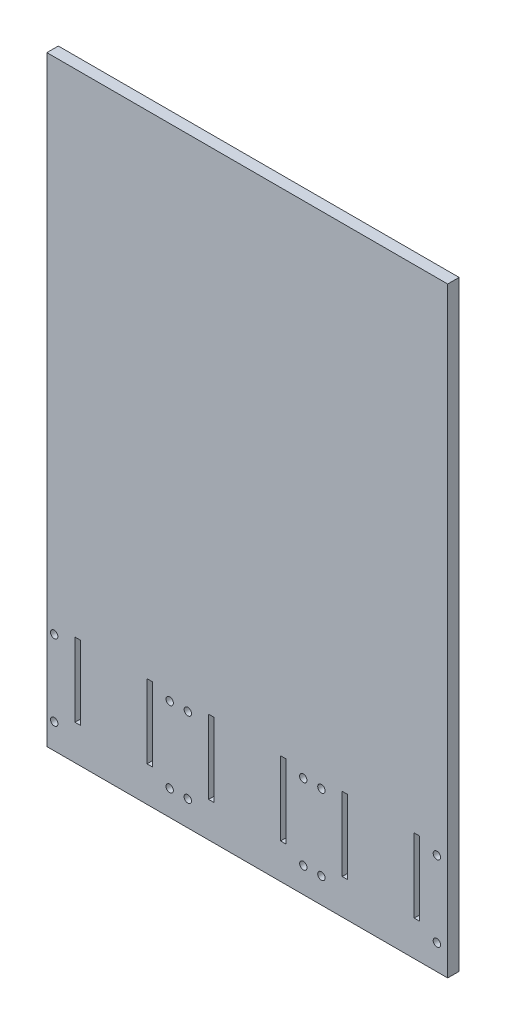
SolidWorks part; units mm, degrees
ref_plane "Front Plane" through (0, 0, 0) normal (0, 0, 1) x (1, 0, 0)
ref_plane "Top Plane" through (0, 0, 0) normal (0, 1, 0) x (1, 0, 0)
ref_plane "Right Plane" through (0, 0, 0) normal (1, 0, 0) x (0, 0, -1)
sketch "Sketch1" plane through (0, 0, 0) normal (0, 0, 1) x (1, 0, 0)
  line L0 (111.3, -111.5408) -> (111.3, 222.2553)
  line L1 (111.3, -111.5408) -> (-111.3, -111.5408)
  line L2 (111.3, 222.2553) -> (-111.3, 222.2553)
  line L3 (-111.3, -111.5408) -> (-111.3, 222.2553)
  line L4 (111.3, -111.5408) -> (-111.3, 222.2553) construction
  line L5 (111.3, 222.2553) -> (-111.3, -111.5408) construction
  line L6 (-95.7, -103.393) -> (-95.7, -89.9338) construction
  line L7 (-95.7, -51.0408) -> (-92.7, -51.0408)
  line L8 (-95.7, -51.0408) -> (-95.7, -92.0408)
  line L9 (-95.7, -92.0408) -> (-92.7, -92.0408)
  line L10 (-92.7, -51.0408) -> (-92.7, -92.0408)
  line L11 (-92.7, -104.2814) -> (-92.7, -92.5342) construction
  line L12 (-95.7, -51.5408) -> (-92.7, -51.5408) construction
  line L13 (-55.7, -107.2088) -> (-55.7, -104.2814) construction
  line L14 (-55.7, -51.0408) -> (-52.7, -51.0408)
  line L15 (-55.7, -51.0408) -> (-55.7, -92.0408)
  line L16 (-55.7, -92.0408) -> (-52.7, -92.0408)
  line L17 (-52.7, -51.0408) -> (-52.7, -92.0408)
  line L18 (-52.7, -103.393) -> (-52.7, -89.9338) construction
  line L20 (-52.7, -51.5408) -> (-55.7, -51.5408) construction
  line L22 (18.5, -51.0408) -> (18.5, -92.0408)
  line L23 (18.5, -51.0408) -> (21.5, -51.0408)
  line L24 (21.5, -51.0408) -> (21.5, -92.0408)
  line L25 (18.5, -92.0408) -> (21.5, -92.0408)
  line L26 (-21.5, -51.0408) -> (-21.5, -92.0408)
  line L27 (-21.5, -51.0408) -> (-18.5, -51.0408)
  line L28 (-18.5, -51.0408) -> (-18.5, -92.0408)
  line L29 (-21.5, -92.0408) -> (-18.5, -92.0408)
  line L30 (92.7, -51.0408) -> (92.7, -92.0408)
  line L31 (92.7, -51.0408) -> (95.7, -51.0408)
  line L32 (95.7, -51.0408) -> (95.7, -92.0408)
  line L33 (92.7, -92.0408) -> (95.7, -92.0408)
  line L34 (52.7, -51.0408) -> (52.7, -92.0408)
  line L35 (52.7, -51.0408) -> (55.7, -51.0408)
  line L36 (55.7, -51.0408) -> (55.7, -92.0408)
  line L37 (52.7, -92.0408) -> (55.7, -92.0408)
  point P1 (0, 0)
  point P9 (0, 0)
  point P23 (0, 0)
  point P27 (0, 0)
  dimension "D1" = 222.6
  dimension "D2" = 0.5
  dimension "D3" = 41
  dimension "D4" = 41
  dimension "D5" = 0.5
  dimension "D6" = 3
extrude "Boss-Extrude1" add sketch "Sketch1" along normal blind 6.35
sketch "Sketch2" plane through (0, 0, 0) normal (0, 0, -1) x (-1, 0, 0)
  line L0 (-111.3, -96.0005) -> (-37.1, -96.0005) construction
  line L1 (-111.3, -111.5408) -> (-111.3, 222.2553) construction
  line L2 (-73.2331, -96.0005) -> (-73.2331, -35.021) construction
  circle A0 centre (-105.3, -97.5408) radius 2.05
  circle A1 centre (-105.3, -55.5408) radius 2.05
  arc A2 (-103.45, -55.5408) -> (-103.6551, -56.3874) centre (-105.3, -55.5408) ccw construction
  circle A3 centre (-41.1662, -97.5408) radius 2.05
  circle A4 centre (-41.1662, -55.5408) radius 2.05
  circle A5 centre (-31.1, -97.5408) radius 2.05
  circle A6 centre (-31.1, -55.5408) radius 2.05
  circle A7 centre (33.0338, -97.5408) radius 2.05
  circle A8 centre (33.0338, -55.5408) radius 2.05
  circle A9 centre (43.1, -97.5408) radius 2.05
  circle A10 centre (43.1, -55.5408) radius 2.05
  circle A11 centre (107.2338, -97.5408) radius 2.05
  circle A12 centre (107.2338, -55.5408) radius 2.05
  dimension "D1" = 4.1
  dimension "D2" = 74.2
  dimension "D3" = 3
extrude "Cut-Extrude1" cut sketch "Sketch2" against normal blind 10
equation "\"D4@Sketch1\"=\"D3@Sketch1\""
